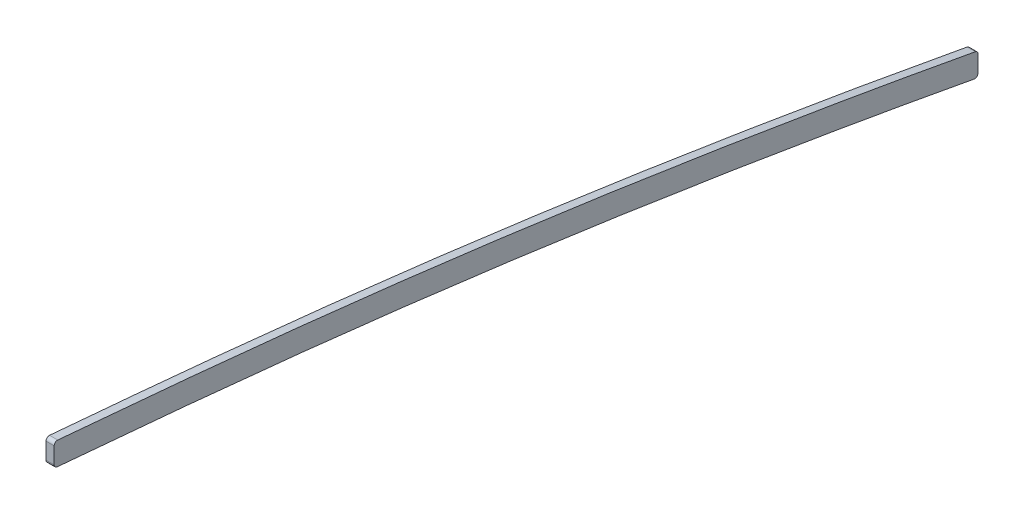
SolidWorks part; units mm, degrees
ref_plane "Front Plane" through (0, 0, 0) normal (0, 0, 1) x (1, 0, 0)
ref_plane "Top Plane" through (0, 0, 0) normal (0, 1, 0) x (1, 0, 0)
ref_plane "Right Plane" through (0, 0, 0) normal (1, 0, 0) x (0, 0, -1)
sketch "Sketch2" plane through (0, 0, 0) normal (1, 0, 0) x (0, 0, -1)
  line L0 (2794, -12.7) -> (0, -12.7)
  line L1 (0, 12.7) -> (2794, 12.7)
  line L2 (0, -12.7) -> (0, 12.7)
  line L3 (99.06, 65.345) -> (99.06, 75.0357)
  line L4 (2669.54, 30.4321) -> (2669.54, 39.4761)
  line L5 (2311.4, 87.2885) -> (2311.4, 78.3664)
  arc A0 (47.6236, 51.8639) -> (46.17, 51.0862) centre (81.3294, -12.8832) ccw
  arc A1 (46.17, 51.0862) -> (42.454, 48.8983) centre (81.3033, -12.8358) ccw
  arc A2 (604.515, 139.4337) -> (596.5837, 139.4794) centre (529.8377, -12134.2803) ccw
  arc A3 (50.452, 43.2954) -> (47.189, 41.3742) centre (81.3033, -12.8358) ccw
  arc A4 (51.7287, 43.9784) -> (50.452, 43.2954) centre (81.3294, -12.8832) ccw
  arc A5 (604.4609, 130.5438) -> (596.5354, 130.5895) centre (529.8377, -12134.2803) ccw
  spline S0 degree 3 poles (42.454, 48.8983) (38.8087, 46.6043) (35.3922, 44.0059) (29.013, 38.2192) (26.0797, 35.0549) (23.4257, 31.6631) knots 0 0 0 0 0.5 0.5 1 1 1 1
  spline S1 degree 3 poles (50.6762, 53.3638) (49.647, 52.8875) (48.6295, 52.3876) (47.6236, 51.8639) knots 0 0 0 0 1 1 1 1
  spline S2 degree 3 poles (50.6762, 53.3638) (57.4619, 56.5022) (64.2646, 59.6027) (77.8982, 65.7412) (84.7292, 68.779) (91.5775, 71.7785) knots 0 0 0 0 0.5 0.5 1 1 1 1
  spline S3 degree 3 poles (135.1572, 90.0546) (146.0437, 94.3752) (156.9989, 98.5043) (173.5662, 104.3226) (179.1109, 106.1998) (190.2486, 109.8197) (195.8415, 111.5623) (207.0655, 114.9013) (212.698, 116.4984) (224.006, 119.5405) (229.6832, 120.9862) (246.7672, 125.0777) (258.2252, 127.4823) (269.7699, 129.479) knots 0 0 0 0 0.25 0.25 0.375 0.375 0.5 0.5 0.625 0.625 0.75 0.75 1 1 1 1
  spline S4 degree 3 poles (107.0497, 78.4661) (116.3733, 82.4386) (125.7374, 86.3161) (135.1572, 90.0546) knots 0 0 0 0 1 1 1 1
  spline S5 degree 3 poles (91.5775, 71.7785) (94.2324, 72.9414) (98.1371, 74.6408) (103.2975, 76.8633) (105.7985, 77.9329) (107.0497, 78.4661) knots 0 0 0 0 0.515864 0.757931 1 1 1 1
  spline S6 degree 3 poles (269.7699, 129.479) (274.1234, 130.2319) (278.4857, 130.9259) (287.228, 132.196) (291.6086, 132.772) (300.3818, 133.8184) (304.7746, 134.289) (313.5678, 135.1544) (317.9679, 135.5494) (322.3695, 135.9285) knots 0 0 0 0 0.25 0.25 0.5 0.5 0.75 0.75 1 1 1 1
  spline S7 degree 3 poles (322.3695, 135.9285) (327.0734, 136.3334) (331.7813, 136.6898) (336.4922, 137.003) knots 0 0 0 0 1 1 1 1
  spline S8 degree 3 poles (1110.4182, 139.2745) (1129.952, 139.2456) (1149.4859, 139.212) (1188.5536, 139.1159) (1208.0873, 139.0527) (1227.621, 138.955) knots 0 0 0 0 0.5 0.5 1 1 1 1
  spline S9 degree 3 poles (336.4922, 137.003) (349.7829, 137.8865) (363.0943, 138.4237) (376.4101, 138.754) knots 0 0 0 0 1 1 1 1
  spline S10 degree 3 poles (768.7401, 138.4684) (782.9768, 138.4603) (797.2135, 138.4795) (825.6867, 138.5497) (839.9233, 138.6001) (868.3963, 138.719) (882.6328, 138.7896) (911.1057, 138.9396) (925.3422, 139.0185) (953.8152, 139.1601) (968.0517, 139.2222) (996.5249, 139.31) (1010.7616, 139.335) (1039.2349, 139.3496) (1053.4716, 139.3405) (1081.9449, 139.3137) (1096.1815, 139.2957) (1110.4182, 139.2745) knots 0 0 0 0 0.125 0.125 0.25 0.25 0.375 0.375 0.5 0.5 0.625 0.625 0.75 0.75 0.875 0.875 1 1 1 1
  spline S11 degree 3 poles (376.4101, 138.754) (383.7263, 138.9356) (391.0438, 139.0556) (405.6796, 139.2242) (412.9979, 139.2729) (420.3162, 139.3058) knots 0 0 0 0 0.5 0.5 1 1 1 1
  spline S12 degree 3 poles (630.7784, 139.2514) (653.7718, 139.0753) (676.765, 138.8717) (711.2553, 138.6477) (722.7522, 138.5862) (745.7461, 138.4998) (757.2431, 138.475) (768.7401, 138.4684) knots 0 0 0 0 0.5 0.5 0.75 0.75 1 1 1 1
  spline S13 degree 3 poles (420.3162, 139.3058) (422.4132, 139.3152) (426.3958, 139.3304) (430.3784, 139.3421) (432.2639, 139.3471) knots 0 0 0 0 0.526549 1 1 1 1
  spline S14 degree 3 poles (604.515, 139.4337) (609.9407, 139.4007) (618.6952, 139.3421) (627.4497, 139.2769) (630.7784, 139.2514) knots 0 0 0 0 0.619766 1 1 1 1
  spline S15 degree 3 poles (432.2639, 139.3471) (433.5536, 139.3506) (434.8433, 139.3539) (436.133, 139.3572) knots 0 0 0 0 1 1 1 1
  spline S16 degree 3 poles (436.133, 139.3572) (449.5039, 139.3907) (462.8749, 139.4124) (489.6167, 139.4986) (502.9875, 139.5591) (529.7293, 139.628) (543.1002, 139.6392) (569.8421, 139.601) (583.213, 139.552) (596.5837, 139.4794) knots 0 0 0 0 0.25 0.25 0.5 0.5 0.75 0.75 1 1 1 1
  spline S17 degree 3 poles (1227.621, 138.955) (1248.8073, 138.8489) (1269.9936, 138.7012) (1312.3638, 138.2707) (1333.5477, 137.9874) (1375.9124, 137.2493) (1397.0931, 136.7926) (1439.4513, 135.7019) (1460.629, 135.0692) (1502.9791, 133.6705) (1524.1522, 132.9074) (1566.4943, 131.2847) (1587.6632, 130.4232) (1651.1641, 127.7091) (1693.4904, 125.7283) (1735.8113, 123.6237) knots 0 0 0 0 0.125 0.125 0.25 0.25 0.375 0.375 0.5 0.5 0.625 0.625 0.75 0.75 1 1 1 1
  spline S18 degree 3 poles (1735.8113, 123.6237) (1776.1386, 121.6183) (1816.4603, 119.5006) (1897.0937, 115.0876) (1937.4056, 112.793) (2018.0184, 108.0184) (2058.3195, 105.5391) (2138.9038, 100.3072) (2179.1874, 97.5551) (2239.587, 93.0802) (2259.7163, 91.5298) (2289.9004, 89.0908) (2299.9602, 88.2588) (2320.076, 86.5529) (2330.1321, 85.679) (2350.2394, 83.8743) (2360.2905, 82.9433) (2380.386, 81.0032) (2390.4301, 79.9934) (2420.547, 76.8276) (2440.6065, 74.5337) (2480.6756, 69.5563) (2500.6872, 66.8742) (2540.6543, 61.1502) (2560.611, 58.1098) (2600.4755, 51.7025) (2620.383, 48.3375) (2650.1996, 43.0417) (2660.1312, 41.2345) (2679.9761, 37.5259) (2689.8897, 35.6246) (2699.7923, 33.6648) knots 0 0 0 0 0.125 0.125 0.25 0.25 0.375 0.375 0.5 0.5 0.5625 0.5625 0.59375 0.59375 0.625 0.625 0.65625 0.65625 0.6875 0.6875 0.75 0.75 0.8125 0.8125 0.875 0.875 0.9375 0.9375 0.96875 0.96875 1 1 1 1
  spline S19 degree 1 poles (47.189, 41.3742) (30.427, 26.1847) knots 0 0 1 1 construction
  spline S20 degree 1 poles (54.4091, 45.2955) (51.7287, 43.9784) knots 0 0 1 1 construction
  spline S21 degree 1 poles (54.4091, 45.2955) (95.1442, 63.6354) knots 0 0 1 1 construction
  spline S22 degree 1 poles (95.1442, 63.6354) (110.5345, 70.2875) knots 0 0 1 1 construction
  spline S23 degree 1 poles (110.5345, 70.2875) (138.4366, 81.7916) knots 0 0 1 1 construction
  spline S24 degree 1 poles (138.4366, 81.7916) (271.285, 120.719) knots 0 0 1 1 construction
  spline S25 degree 1 poles (271.285, 120.719) (323.1321, 127.0712) knots 0 0 1 1 construction
  spline S26 degree 1 poles (323.1321, 127.0712) (337.0819, 128.1326) knots 0 0 1 1 construction
  spline S27 degree 1 poles (337.0819, 128.1326) (376.6306, 129.8668) knots 0 0 1 1 construction
  spline S28 degree 1 poles (376.6306, 129.8668) (420.3562, 130.4159) knots 0 0 1 1 construction
  spline S29 degree 1 poles (420.3562, 130.4159) (432.2877, 130.4571) knots 0 0 1 1 construction
  spline S30 degree 1 poles (432.2877, 130.4571) (436.1553, 130.4672) knots 0 0 1 1 construction
  spline S31 degree 1 poles (436.1553, 130.4672) (596.5354, 130.5895) knots 0 0 1 1 construction
  spline S32 degree 1 poles (604.4609, 130.5438) (630.7103, 130.3617) knots 0 0 1 1 construction
  spline S33 degree 1 poles (630.7103, 130.3617) (768.735, 129.5784) knots 0 0 1 1 construction
  spline S34 degree 1 poles (768.735, 129.5784) (1110.405, 130.3845) knots 0 0 1 1 construction
  spline S35 degree 1 poles (1110.405, 130.3845) (1227.5765, 130.0651) knots 0 0 1 1 construction
  spline S36 degree 1 poles (1227.5765, 130.0651) (1735.3698, 114.7447) knots 0 0 1 1 construction
  spline S37 degree 1 poles (1735.3698, 114.7447) (2698.0664, 24.9439) knots 0 0 1 1 construction
  spline S38 degree 3 poles (30.427, 26.1847) (31.5989, 27.6824) (34.071, 30.5835) (38.124, 34.5916) (42.486, 38.2181) (45.592, 40.3693) (47.189, 41.3742) knots -0.000002 -0.000002 -0.000002 -0.000002 0.249999 0.499999 0.75 1 1 1 1
  spline S39 degree 3 poles (51.7287, 43.9784) (51.9494, 44.0933) (52.3923, 44.3206) (53.0604, 44.6537) (53.7324, 44.9791) (54.1832, 45.1909) (54.4091, 45.2955) knots 0.000384 0.000384 0.000384 0.000384 0.25029 0.500196 0.750102 1.000008 1.000008 1.000008 1.000008
  spline S40 degree 3 poles (54.4091, 45.2955) (57.7875, 46.858) (64.5519, 49.9638) (74.7284, 54.5738) (84.9254, 59.1368) (91.7348, 62.1421) (95.1442, 63.6354) knots 0.000027 0.000027 0.000027 0.000027 0.250021 0.500014 0.750007 1 1 1 1
  spline S41 degree 3 poles (95.1442, 63.6354) (96.1287, 64.0666) (97.7542, 64.7769) (100.3172, 65.8923) (103.1775, 67.132) (106.6816, 68.6417) (109.2496, 69.74) (110.5345, 70.2875) knots 0 0 0 0 0.192239 0.317239 0.5 0.75 1 1 1 1
  spline S42 degree 3 poles (110.5345, 70.2875) (112.8507, 71.2744) (117.4893, 73.2368) (124.4567, 76.1381) (131.4385, 78.9943) (136.1012, 80.8648) (138.4366, 81.7916) knots 0 0 0 0 0.25 0.5 0.75 1 1 1 1
  spline S43 degree 3 poles (138.4366, 81.7916) (143.8269, 83.9309) (154.6523, 88.1188) (176.4082, 96.0376) (203.9068, 104.9982) (237.3947, 114.0271) (259.9348, 118.756) (271.285, 120.719) knots 0 0 0 0 0.125 0.25 0.5 0.75 1 1 1 1
  spline S44 degree 3 poles (271.285, 120.719) (275.5587, 121.4581) (284.1243, 122.8211) (297.0364, 124.5189) (310.0184, 125.9099) (318.7666, 126.6953) (323.1321, 127.0712) knots 0 0 0 0 0.249999 0.499998 0.749998 0.999997 0.999997 0.999997 0.999997
  spline S45 degree 3 poles (323.1321, 127.0712) (324.2931, 127.1712) (326.6152, 127.365) (330.1016, 127.6385) (333.5902, 127.8951) (335.918, 128.0552) (337.0819, 128.1326) knots 0.000012 0.000012 0.000012 0.000012 0.250009 0.500006 0.750003 1 1 1 1
  spline S46 degree 3 poles (337.0819, 128.1326) (340.3679, 128.351) (346.9399, 128.7449) (356.8213, 129.2212) (366.7163, 129.5951) (373.3266, 129.7848) (376.6306, 129.8668) knots 0 0 0 0 0.25 0.5 0.75 1 1 1 1
  spline S47 degree 3 poles (376.6306, 129.8668) (380.2664, 129.957) (387.5348, 130.1068) (398.4622, 130.2594) (409.401, 130.3587) (416.7054, 130.3994) (420.3562, 130.4159) knots 0 0 0 0 0.25 0.5 0.75 1 1 1 1
  spline S48 degree 3 poles (420.3562, 130.4159) (421.35, 130.4203) (423.3375, 130.4286) (426.3202, 130.4394) (429.3035, 130.4489) (431.293, 130.4545) (432.2877, 130.4571) knots 0 0 0 0 0.25 0.5 0.75 1 1 1 1
  spline S49 degree 3 poles (432.2877, 130.4571) (432.61, 130.458) (433.2547, 130.4597) (434.2216, 130.4623) (435.1885, 130.4648) (435.833, 130.4664) (436.1553, 130.4672) knots 0 0 0 0 0.25 0.5 0.75 1 1 1 1
  spline S50 degree 3 poles (436.1553, 130.4672) (449.5283, 130.5007) (476.2757, 130.5466) (516.389, 130.7288) (556.4563, 130.7597) (583.1765, 130.6621) (596.5354, 130.5895) knots 0 0 0 0 0.25 0.5 0.75 1 1 1 1
  spline S51 degree 3 poles (604.4609, 130.5438) (606.6482, 130.5306) (611.0225, 130.5029) (617.5847, 130.4584) (624.1472, 130.4113) (628.5227, 130.3785) (630.7103, 130.3617) knots -0.000001 -0.000001 -0.000001 -0.000001 0.249999 0.5 0.75 1 1 1 1
  spline S52 degree 3 poles (630.7103, 130.3617) (642.2061, 130.2736) (665.1936, 130.0838) (699.6991, 129.8192) (734.215, 129.6347) (757.2286, 129.585) (768.735, 129.5784) knots 0 0 0 0 0.25 0.5 0.75 1 1 1 1
  spline S53 degree 3 poles (768.735, 129.5784) (797.2224, 129.5621) (854.2037, 129.7251) (939.6352, 130.2366) (1024.993, 130.5249) (1081.9376, 130.4268) (1110.405, 130.3845) knots 0 0 0 0 0.25 0.5 0.75 1 1 1 1
  spline S54 degree 3 poles (1110.405, 130.3845) (1120.1708, 130.3701) (1139.7031, 130.3388) (1168.9984, 130.2777) (1198.2906, 130.1944) (1217.8142, 130.1139) (1227.5765, 130.0651) knots 0 0 0 0 0.25 0.5 0.75 1 1 1 1
  spline S55 degree 3 poles (1227.5765, 130.0651) (1269.9112, 129.8532) (1333.4277, 129.2734) (1418.0422, 127.4491) (1502.666, 124.9136) (1608.4542, 120.8033) (1693.0701, 116.8482) (1735.3698, 114.7447) knots 0 0 0 0 0.25 0.375 0.5 0.75 1 1 1 1
  spline S56 degree 3 poles (1735.3698, 114.7447) (1815.9959, 110.7352) (1936.9067, 104.0964) (2098.0495, 94.188) (2198.6947, 87.3146) (2264.7604, 82.2221) (2300.6441, 79.2861) (2321.4466, 77.5184) (2355.8702, 74.4619) (2400.272, 70.2017) (2479.5705, 61.1274) (2559.2921, 49.6509) (2626.7976, 38.2355) (2659.2727, 32.3571) (2679.0625, 28.6522) (2690.9404, 26.3542) (2698.0664, 24.9439) knots 0 0 0 0 0.25 0.375 0.5 0.5625 0.580337 0.611587 0.627212 0.6875 0.75 0.875 0.9375 0.962411 0.977446 1 1 1 1
  dimension "D1" = 25.4
  dimension "D2" = 8.89
  dimension "D3" = 99.06
  dimension "D4" = 2669.54
  dimension "D5" = 2311.4
extrude "Boss-Extrude1" add sketch "Sketch2" against normal mid plane 3.175 contours L5 S56 L4 S18 region at (0, 62.0118, -2490.8839)
fillet "Fillet1" radius 1.27 4 edges at (0, 78.3664, -2311.4) (0, 30.4321, -2669.54)
